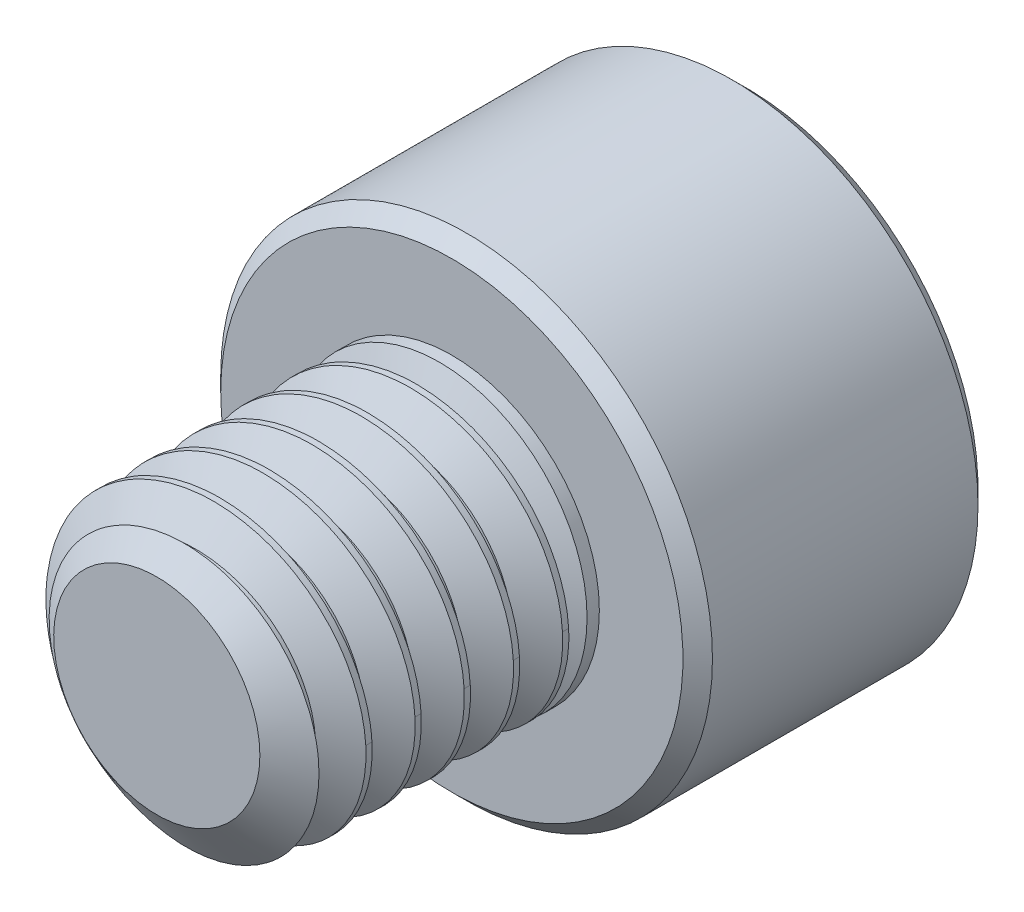
SolidWorks part; units mm, degrees
ref_plane "Front Plane" through (0, 0, 0) normal (0, 0, 1) x (1, 0, 0)
ref_plane "Top Plane" through (0, 0, 0) normal (0, 1, 0) x (1, 0, 0)
ref_plane "Right Plane" through (0, 0, 0) normal (1, 0, 0) x (0, 0, -1)
sketch "Sketch1" plane through (0, 0, 0) normal (0, 0, 1) x (1, 0, 0)
  circle A0 centre (0, 0) radius 3
  dimension "OD" = 6
extrude "Extrude1" add sketch "Sketch1" against normal blind 6
sketch "Sketch2" plane through (0, 0, 0) normal (0, 0, 1) x (1, 0, 0)
  circle A0 centre (0, 0) radius 3 construction
  circle A1 centre (0, 0) radius 3
curve "Helix/Spiral1" pitch 1 height 7 turns 7 parameters "pitch"=1
sketch "Sketch3" plane through (0, 0, 0) normal (1, 0, 0) x (0, 0, -1)
  line L0 (-0.875, 3) -> (-0.5, 2.3505)
  line L1 (-0.5, 2.3505) -> (-0.375, 2.3505)
  line L2 (-0.375, 2.3505) -> (0, 3)
  line L3 (-0.875, 3) -> (0, 3)
  line L4 (-0.4375, 3) -> (-0.4375, 2.3505) construction
  line L5 (-0.6875, 2.6752) -> (-0.1875, 2.6752) construction
  line L6 (0, 3) -> (0, -3) construction
  line L7 (0, -3) -> (6, -3) construction
  point P11 (4.5, -3)
  dimension "D1" = 0.125
  dimension "D2" = 0.5
  dimension "D3" = 60
  dimension "D4" = 4.5
sweep "Cut-Sweep1" cut profiles "Sketch3" path "Helix/Spiral1"
sketch "Sketch4" plane through (0, 0, 0) normal (1, 0, 0) x (0, 0, -1)
  line L0 (0.6327, 3) -> (0, 2.0965)
  line L1 (0, 2.0965) -> (0, 3)
  line L2 (0.6327, 3) -> (0, 3)
  line L3 (-0.875, 3) -> (0, 3) construction
  line L4 (0, 0) -> (7.0209, 0) construction
  dimension "D1" = 55
  dimension "D2" = 0.254
revolve "Cut-Revolve1" cut sketch "Sketch4" angle 360 about L4
sketch "Sketch5" plane through (0, 0, 0) normal (1, 0, 0) x (0, 0, -1)
  line L0 (6, -2.3644) -> (6, 2.1406) construction
  line L1 (6, 3) -> (0.1203, 3)
  line L2 (6, 3) -> (6, 0)
  line L3 (6, 0) -> (0.0001, 0)
  line L4 (0.0001, 2.6698) -> (0.0001, 0)
  line L5 (0.1203, 3) -> (0.0001, 2.6698)
  line L6 (0, 0) -> (9.9695, 0) construction
  point P3 (0.0001, 3)
  point P10 (0.0001, 3)
  dimension "D1" = 0.3302
  dimension "Thread min" = 0.0001
  dimension "D3" = 20
revolve "partially thread" [suppressed] add sketch "Sketch5" angle 360 about L6
sketch "Sketch6" plane through (0, 0, -6) normal (0, 0, -1) x (-1, 0, 0)
  circle A0 centre (0, 0) radius 5
  dimension "head dia" = 10
extrude "Extrude2" add sketch "Sketch6" along normal blind 6
sketch "Sketch7" plane through (0, 0, -12) normal (0, 0, -1) x (-1, 0, 0)
  line L1 (0, 2.8868) -> (-2.5, 1.4434)
  line L2 (-2.5, 1.4434) -> (-2.5, -1.4434)
  line L3 (-2.5, -1.4434) -> (0, -2.8868)
  line L4 (0, -2.8868) -> (2.5, -1.4434)
  line L5 (2.5, -1.4434) -> (2.5, 1.4434)
  line L6 (2.5, 1.4434) -> (0, 2.8868)
  circle A0 centre (0, 0) radius 2.5 construction
  dimension "hex dia" = 5
extrude "Cut-Extrude1" cut sketch "Sketch7" against normal blind 3.75
sketch "Sketch8" plane through (0, 0, -12) normal (0, 0, -1) x (-1, 0, 0)
  circle A0 centre (0, 0) radius 2.8868
extrude "Cut-Extrude2" cut sketch "Sketch8" against normal through all draft 45
chamfer "Chamfer1" distance 0.3 angle 45 2 edges at (-5, 0, -12) (-5, 0, -6)
sketch "Sketch9" plane through (0, 0, 0) normal (1, 0, 0) x (0, 0, -1)
  line L0 (0, 3) -> (0, -3) construction
  line L1 (5.5, 3) -> (5.5, -3) construction
  dimension "D1" = 5.5
sketch "Sketch10" plane through (0, 0, 0) normal (1, 0, 0) x (0, 0, -1)
  line L0 (6, 3) -> (6, 0)
  line L1 (6, 3) -> (5.75, 3)
  line L2 (5.75, 3) -> (4.5074, 0)
  line L3 (6, 0) -> (4.5074, 0)
  line L4 (6, 4.7) -> (6, -4.7) construction
  dimension "D1" = 22.5
  dimension "D2" = 0.25
revolve "Revolve1" add sketch "Sketch10" angle 360 about L3
equation "\"D3@Helix/Spiral1\" = \"screw length@Extrude1\"+\"pitch@Helix/Spiral1\""
equation "\"D1@Sketch3\" = \"pitch@Helix/Spiral1\"*.125"
equation "\"D2@Sketch3\" = \"pitch@Helix/Spiral1\"*.5"
equation "\"D1@Cut-Extrude1\" = \"hex dia@Sketch7\"*.75"
equation "\"D1@Chamfer1\" = \"head dia@Sketch6\"*.03"
equation "\"D1@Sketch9\" = \"pitch@Helix/Spiral1\"*5.5"
equation "\"D2@Sketch10\" = \"pitch@Helix/Spiral1\"*.25"
equation "\"D4@Sketch3\" = \"pitch@Helix/Spiral1\"*4.50"
